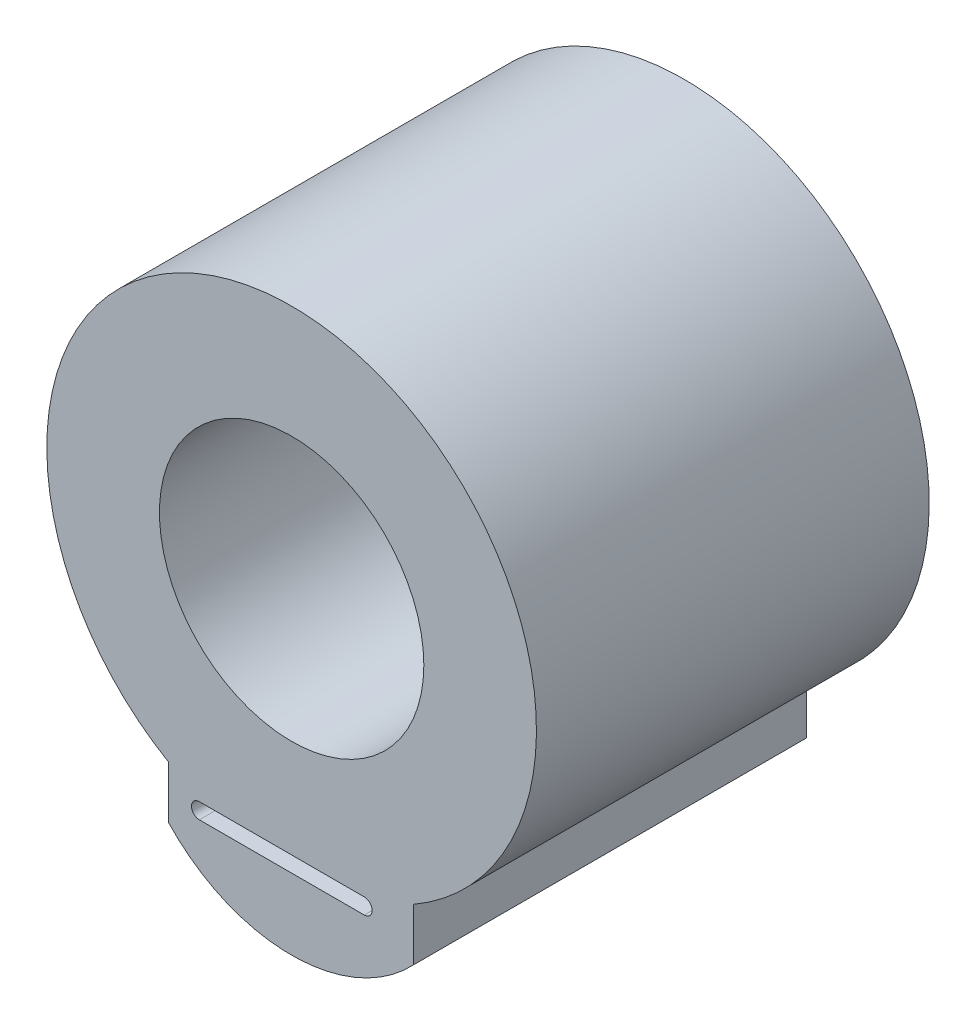
SolidWorks part; units mm, degrees
ref_plane "Front Plane" through (0, 0, 0) normal (0, 0, 1) x (1, 0, 0)
ref_plane "Top Plane" through (0, 0, 0) normal (0, 1, 0) x (1, 0, 0)
ref_plane "Right Plane" through (0, 0, 0) normal (1, 0, 0) x (0, 0, -1)
sketch "Sketch1" plane through (0, 0, 0) normal (0, 0, 1) x (1, 0, 0)
  line L3 (11.842, -25.6671) -> (11.842, -20.5871)
  line L5 (-11.9493, -25.605) -> (-11.9493, -20.525)
  arc A0 (11.842, -20.5871) -> (-11.9493, -20.525) centre (0, 0) ccw
  circle A1 centre (0, 0) radius 12.8241
  arc A4 (-11.9493, -25.605) -> (11.842, -25.6671) centre (-0.0245, -14.478) ccw
  dimension "D1" = 25.6483
  dimension "D2" = 23.75
  dimension "D3" = 16.3099
  dimension "D4" = 5.08
  dimension "D5" = 11.9493
  dimension "D6" = 14.478
  dimension "D7" = 5.08
extrude "Boss-Extrude2" add sketch "Sketch1" along normal blind 38.1
sketch "Sketch3" plane through (0, 0, 38.1) normal (0, 0, 1) x (1, 0, 0)
  line L0 (-8.9539, -23.1251) -> (7.0461, -23.1251) construction
  line L1 (-8.9539, -22.3631) -> (7.0461, -22.3631)
  line L2 (-8.9539, -23.8871) -> (7.0461, -23.8871)
  line L3 (11.842, -25.6671) -> (11.842, -20.5871) construction
  arc A0 (-8.9539, -22.3631) -> (-8.9539, -23.8871) centre (-8.9539, -23.1251) ccw
  arc A1 (7.0461, -23.8871) -> (7.0461, -22.3631) centre (7.0461, -23.1251) ccw
  point P2 (-0.9539, -23.1251)
  dimension "D3" = 1.524
  dimension "D4" = 4.7959
  dimension "D1" = 16
  dimension "D2" = 23.1251
extrude "Cut-Extrude1" cut sketch "Sketch3" against normal blind 35
sketch "Sketch6" plane through (0, -23.8871, 0) normal (0, 1, 0) x (1, 0, 0)
  circle A0 centre (0, -9.092) radius 8
  point P2 (0, -9.092)
extrude "Cut-Extrude2" cut sketch "Sketch6" along normal blind 23.57 and the other way blind 23.57
